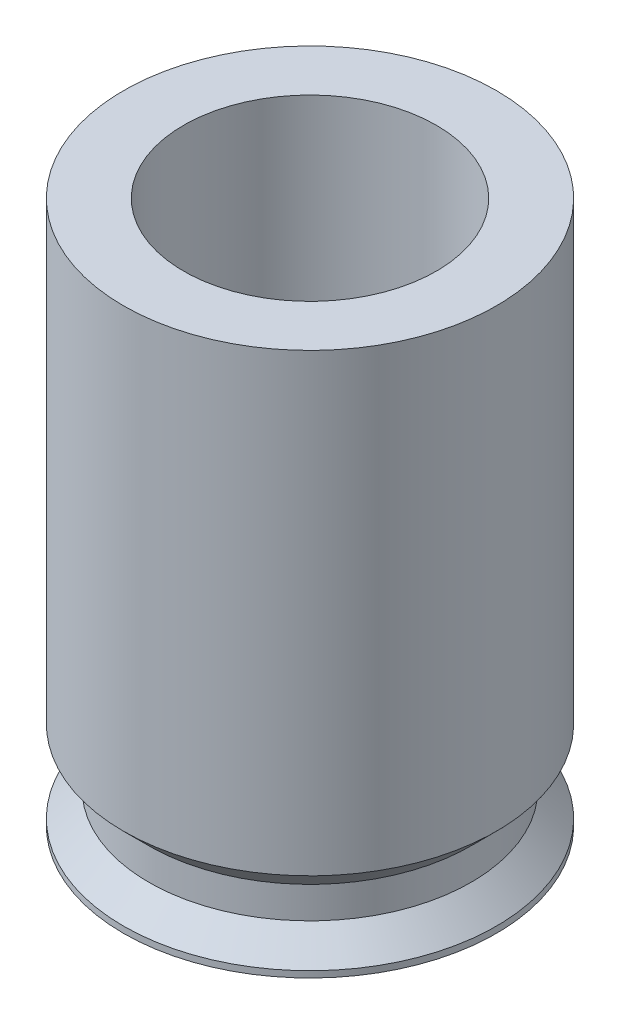
SolidWorks part; units mm, degrees
material "铸造碳钢"
ref_plane "前视基准面" through (0, 0, 0) normal (0, 0, 1) x (1, 0, 0)
ref_plane "上视基准面" through (0, 0, 0) normal (0, 1, 0) x (1, 0, 0)
ref_plane "右视基准面" through (0, 0, 0) normal (1, 0, 0) x (0, 0, -1)
sketch "草图1" plane through (0, 0, 0) normal (0, 1, 0) x (1, 0, 0)
  circle A0 centre (0, 0) radius 2
  circle A1 centre (0, 0) radius 2.95
  dimension "螺纹型号" = 4
  dimension "最大外径" = 5.9
extrude "凸台-拉伸1" add sketch "草图1" along normal mid plane 8.6
sketch "草图2" plane through (0, 0, 0) normal (1, 0, 0) x (0, 0, -1)
  line L0 (-6.4064, 0) -> (6.4064, 0) construction
  line L1 (0, -1000) -> (0, 49000) construction
  line L2 (-2.95, -3.3) -> (-2.55, -3.3)
  line L3 (-2.95, -3.3) -> (-2.95, -3.8)
  line L4 (-2.95, -3.8) -> (-2.55, -3.8)
  line L5 (-2.55, -3.3) -> (-2.55, -3.8)
  line L6 (-2.95, 4.3) -> (-2.95, -4.3) construction
  line L8 (-2.95, -4.3) -> (2.95, -4.3) construction
  point P4 (0, 0)
  dimension "D1" = 0.4
  dimension "D2" = 0.5
  dimension "D3" = 0.5
revolve "切除-旋转1" cut sketch "草图2" angle 360 about L1
chamfer "倒角1" distance 0.4 angle 45 2 edges at (0, -3.8, -2.95) (0, -3.3, -2.95)
other "冻结***"
